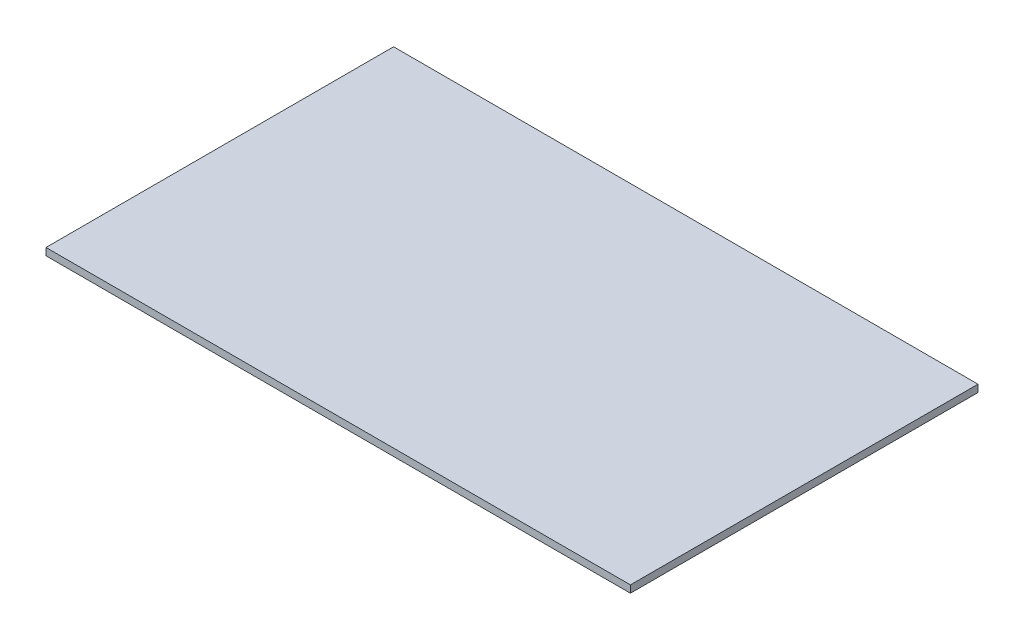
SolidWorks part; units mm, degrees
material "ABS PC"
ref_plane "X-Y Datum" through (0, 0, 0) normal (0, 0, 1) x (1, 0, 0)
ref_plane "X-Z Datum" through (0, 0, 0) normal (0, 1, 0) x (1, 0, 0)
ref_plane "Y-Z Datum" through (0, 0, 0) normal (1, 0, 0) x (0, 0, -1)
sketch "Sketch1" plane through (0, 0, 0) normal (0, 0, 1) x (1, 0, 0)
  line L1 (-128.1214, -1.5875) -> (128.1214, -1.5875)
  line L2 (-128.1214, -1.5875) -> (-128.1214, 1.5875)
  line L3 (-128.1214, 1.5875) -> (128.1214, 1.5875)
  line L4 (128.1214, -1.5875) -> (128.1214, 1.5875)
  line L5 (-128.1214, -1.5875) -> (128.1214, 1.5875) construction
  line L6 (-128.1214, 1.5875) -> (128.1214, -1.5875) construction
  point P0 (0, 0)
  dimension "D1" = 256.2428
  dimension "D2" = 3.175
extrude "Boss-Extrude1" add sketch "Sketch1" along normal blind 152.4
